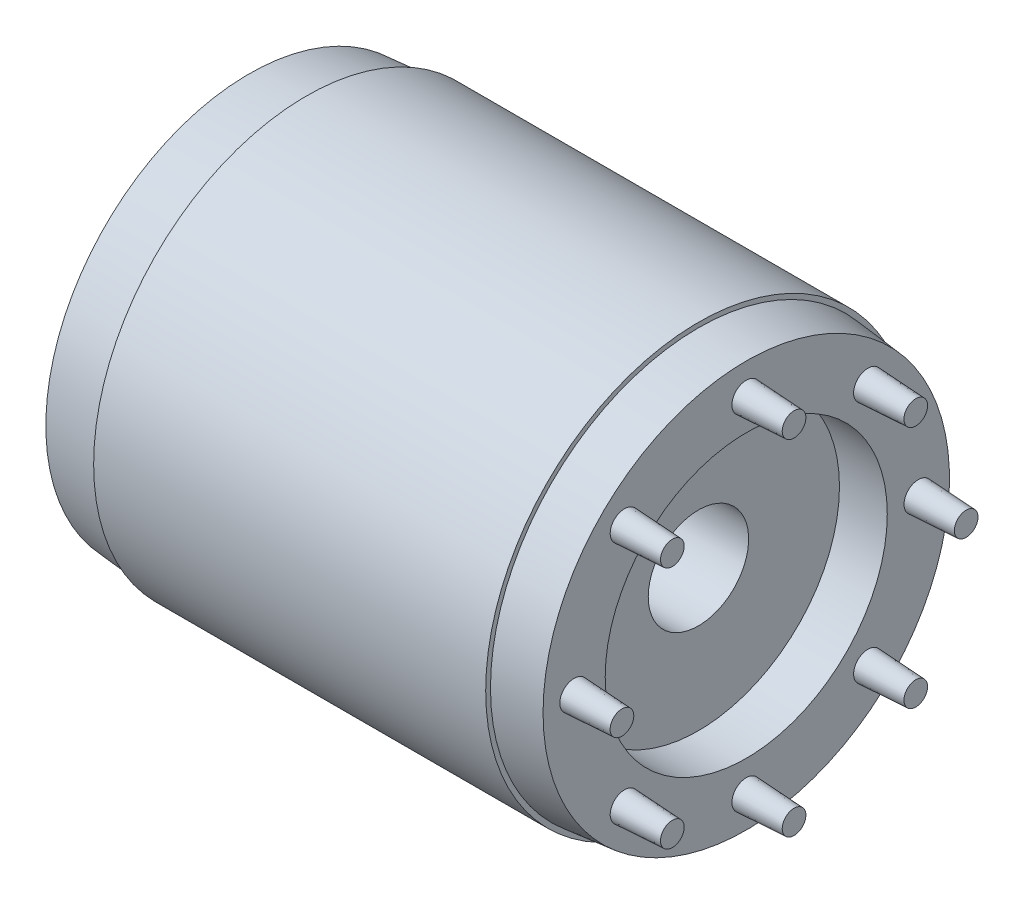
SolidWorks part; units mm, degrees
material "AISI 1020"
ref_plane "Plano frontal" through (0, 0, 0) normal (0, 0, 1) x (1, 0, 0)
ref_plane "Plano superior" through (0, 0, 0) normal (0, 1, 0) x (1, 0, 0)
ref_plane "Plano direito" through (0, 0, 0) normal (1, 0, 0) x (0, 0, -1)
sketch "Esboço1" plane through (0, 0, 0) normal (0, 0, 1) x (1, 0, 0)
  line L0 (0, 0) -> (612.7616, 0) construction
  line L1 (0, 10.5) -> (82, 10.5)
  line L2 (41, 10.5) -> (41, 44.5) construction
  line L3 (0, 10.5) -> (0, 29.5)
  line L4 (-12, 35.5) -> (-3.8962, 35.5)
  line L5 (-12, 35.5) -> (-12, 42.5)
  line L6 (0, 43.5) -> (-12, 42.5)
  line L7 (0, 43.5) -> (0, 44.5)
  line L8 (0, 44.5) -> (82, 44.5)
  line L9 (82, 43.5) -> (82, 44.5)
  line L10 (82, 43.5) -> (92, 42.5)
  line L11 (92, 29.5) -> (92, 42.5)
  line L12 (82, 29.5) -> (82, 10.5)
  line L13 (82, 29.5) -> (92, 29.5)
  line L14 (-3.8962, 35.5) -> (-3.8962, 29.5)
  line L15 (-3.8962, 29.5) -> (0, 29.5)
  dimension "D1" = 21
  dimension "D2" = 89
  dimension "D3" = 82
  dimension "D4" = 12
  dimension "D5" = 7
  dimension "D6" = 10
  dimension "D7" = 1
  dimension "D8" = 6
  dimension "D9" = 1
  dimension "D10" = 1
revolve "Revolução1" add sketch "Esboço1" angle 360 about L0
sketch "Esboço2" plane through (92, 0, 0) normal (1, 0, 0) x (0, 0, -1)
  line L0 (0, 42.5) -> (0, 29.5) construction
  circle A0 centre (0, 0) radius 42.5 construction
  circle A1 centre (0, 0) radius 29.5 construction
  circle A2 centre (0, 36) radius 3
  dimension "D1" = 6
extrude "Extrusão1" add sketch "Esboço2" along normal blind 10 draft 3
ref_axis "Eixo1" through (0, 0, 0) along (1, 0, 0)
pattern_circular "CirPattern1" count 8 over 360 about axis through (0, 0, 0) along (1, 0, 0) of "Extrusão1"
